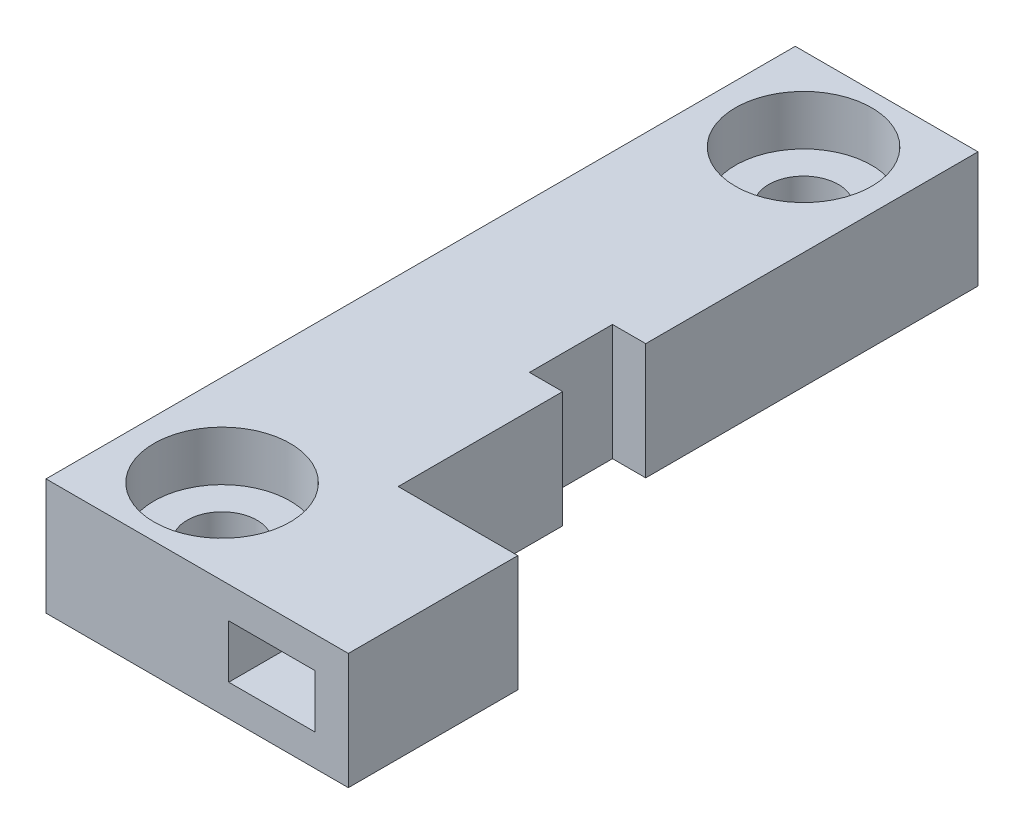
SolidWorks part; units mm, degrees
ref_plane "Front Plane" through (0, 0, 0) normal (0, 0, 1) x (1, 0, 0)
ref_plane "Top Plane" through (0, 0, 0) normal (0, 1, 0) x (1, 0, 0)
ref_plane "Right Plane" through (0, 0, 0) normal (1, 0, 0) x (0, 0, -1)
sketch "Sketch1" plane through (0, 0, 0) normal (0, 1, 0) x (1, 0, 0)
  line L0 (0, 0) -> (18.2, 0)
  line L1 (18.2, 0) -> (18.2, 10.2)
  line L2 (18.2, 10.2) -> (11, 10.2)
  line L4 (11, 45.1) -> (0, 45.1)
  line L5 (0, 45.1) -> (0, 0)
  line L6 (0, 22.55) -> (11, 22.55) construction
  line L7 (11, 45.1) -> (11, 25.1)
  line L8 (11, 25.1) -> (9, 25.1)
  line L9 (9, 25.1) -> (9, 20.1)
  line L10 (9, 20.1) -> (11, 20.1)
  line L11 (11, 20.1) -> (11, 10.2)
  dimension "D1" = 18.2
  dimension "D2" = 10.2
  dimension "D3" = 45.1
  dimension "D4" = 11
  dimension "D5" = 5
  dimension "D6" = 2
  dimension "D7" = 20
  dimension "D8" = 2
extrude "Boss-Extrude1" add sketch "Sketch1" along normal blind 7
sketch "Sketch2" plane through (0, 0, 0) normal (0, 0, 1) x (1, 0, 0)
  line L0 (18.2, 7) -> (18.2, 0) construction
  line L1 (11, 5.1) -> (16.2, 5.1)
  line L2 (11, 5.1) -> (11, 1.9)
  line L3 (11, 1.9) -> (16.2, 1.9)
  line L4 (16.2, 5.1) -> (16.2, 1.9)
  line L6 (11, 7) -> (0, 7) construction
  point P6 (18.2, 3.5)
  point P7 (16.2, 3.5)
  point P10 (5.5, 7)
  dimension "D1" = 5.5
  dimension "D2" = 5.2
  dimension "D3" = 3.2
extrude "Cut-Extrude1" cut sketch "Sketch2" against normal up to next contours L1 L4 L3 L2
sketch "Sketch3" plane through (0, 7, 0) normal (0, 1, 0) x (1, 0, 0)
  line L1 (11, 45.1) -> (0, 45.1) construction
  line L2 (18.2, 0) -> (18.2, 10.2) construction
  circle A0 centre (5.5, 5.1) radius 2.1
  circle A1 centre (5.5, 40.1) radius 2.1
  point P14 (5.5, 45.1)
  point P15 (18.2, 5.1)
  dimension "D1" = 4.2
  dimension "D2" = 35
  dimension "D3" = 4.2
extrude "Cut-Extrude2" cut sketch "Sketch3" against normal up to next contours A1 | A0 region at (5.5, 7, -40.1)
sketch "Sketch4" plane through (0, 7, 0) normal (0, 1, 0) x (1, 0, 0)
  circle A0 centre (5.5, 5.1) radius 4.1
  circle A1 centre (5.5, 40.1) radius 4.1
  dimension "D1" = 8.2
  dimension "D2" = 8.2
extrude "Cut-Extrude3" cut sketch "Sketch4" against normal blind 3
